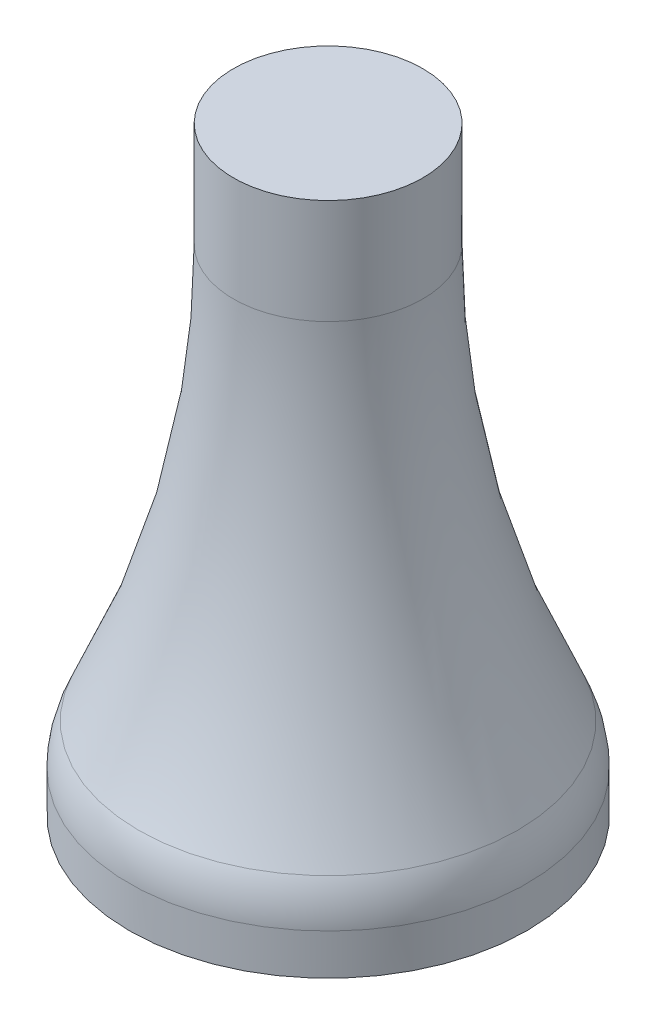
SolidWorks part; units mm, degrees
ref_plane "前视基准面" through (0, 0, 0) normal (0, 0, 1) x (1, 0, 0)
ref_plane "上视基准面" through (0, 0, 0) normal (0, 1, 0) x (1, 0, 0)
ref_plane "右视基准面" through (0, 0, 0) normal (1, 0, 0) x (0, 0, -1)
sketch "草图1" plane through (0, 0, 0) normal (0, 1, 0) x (1, 0, 0)
  circle A0 centre (0, 0) radius 31.5
extrude "凸台-拉伸1" add sketch "草图1" along normal blind 10
sketch "草图3" plane through (0, 0, 0) normal (0, 0, 1) x (1, 0, 0)
  line L0 (0, 0) -> (0, 73.3533) construction
  line L1 (0, 95) -> (15, 95)
  line L2 (15, 95) -> (15, 25)
  line L3 (15, 25) -> (31.5, 10)
  line L4 (31.5, 10) -> (0, 10)
  line L5 (31.5, 10) -> (-31.5, 10) construction
  line L6 (0, 10) -> (0, 95)
  line L7 (31.5, 0) -> (31.5, 10) construction
  dimension "D1" = 85
  dimension "D2" = 15
  dimension "D3" = 70
revolve "旋转1" add sketch "草图3" angle 360 about L0
fillet "圆角1" radius 150 1 edges at (0, 25, -15)
fillet "圆角3" radius 15 1 edges at (0, 10, 31.5)
